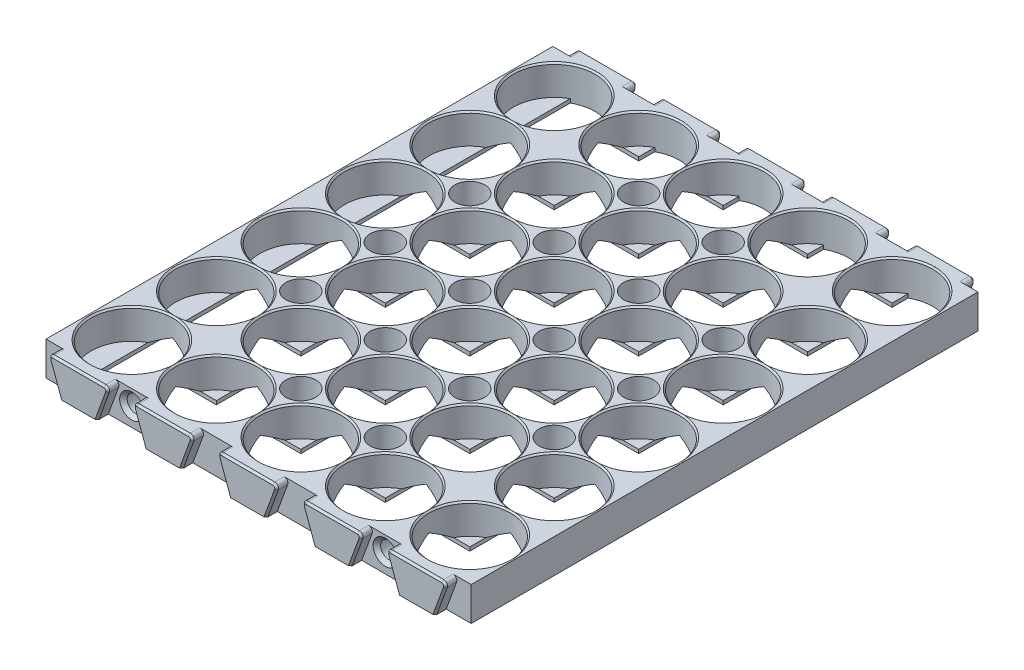
SolidWorks part; units mm, degrees
ref_plane "Front Plane" through (0, 0, 0) normal (0, 0, 1) x (1, 0, 0)
ref_plane "Top Plane" through (0, 0, 0) normal (0, 1, 0) x (1, 0, 0)
ref_plane "Right Plane" through (0, 0, 0) normal (1, 0, 0) x (0, 0, -1)
sketch "Sketch1" plane through (0, 0, 0) normal (0, 1, 0) x (1, 0, 0)
  line L0 (-11.25, 10.875) -> (11.25, 10.875) construction
  line L1 (-11.25, -11.25) -> (11.25, -11.25)
  line L2 (-11.25, -11.25) -> (-11.25, 11.25)
  line L3 (-11.25, 11.25) -> (11.25, 11.25)
  line L4 (11.25, -11.25) -> (11.25, 11.25)
  line L5 (-11.25, -11.25) -> (11.25, 11.25) construction
  line L6 (-11.25, 11.25) -> (11.25, -11.25) construction
  circle A0 centre (0, 0) radius 10.875
  point P0 (0, 0)
  dimension "D1" = 21.75
  dimension "D2" = 22.5
  dimension "D3" = 0.375
extrude "Boss-Extrude1" add sketch "Sketch1" along normal blind 8
sketch "Sketch2" plane through (0, 0, 0) normal (0, -1, 0) x (1, 0, 0)
  line L0 (5.25, 11.25) -> (-5.25, 11.25) construction
  line L1 (11.25, 11.25) -> (5.25, 11.25)
  line L2 (11.25, 11.25) -> (11.25, 5.25)
  line L3 (11.25, 5.25) -> (5.25, 5.25)
  line L4 (5.25, 11.25) -> (5.25, 5.25)
  line L5 (11.25, -11.25) -> (5.25, -11.25)
  line L6 (11.25, -11.25) -> (11.25, -5.25)
  line L7 (11.25, -5.25) -> (5.25, -5.25)
  line L8 (5.25, -11.25) -> (5.25, -5.25)
  line L9 (-11.25, -11.25) -> (-5.25, -11.25)
  line L10 (-11.25, -11.25) -> (-11.25, -5.25)
  line L11 (-11.25, -5.25) -> (-5.25, -5.25)
  line L12 (-5.25, -11.25) -> (-5.25, -5.25)
  line L13 (-11.25, 11.25) -> (-5.25, 11.25)
  line L14 (-11.25, 11.25) -> (-11.25, 5.25)
  line L15 (-11.25, 5.25) -> (-5.25, 5.25)
  line L16 (-5.25, 11.25) -> (-5.25, 5.25)
  line L17 (11.25, 5.25) -> (11.25, -5.25) construction
  line L18 (5.25, -11.25) -> (-5.25, -11.25) construction
  line L19 (-11.25, 5.25) -> (-11.25, -5.25) construction
  dimension "D1" = 10.5
extrude "Boss-Extrude2" add sketch "Sketch2" along normal blind 1
chamfer "Chamfer2" distance 0.4 angle 45 1 edges at (0, 8, 10.875)
pattern_linear "LPattern1" count 6 spacing 22.5 along (0, 0, 1) count 5 spacing 22.5 along (1, 0, 0) of "Boss-Extrude2", "Boss-Extrude1", "Chamfer2"
sketch "Sketch5" plane through (0, 0, -5.25) normal (0, 0, 1) x (1, 0, 0)
  line L25 (-5.25, -1) -> (-5.25, 0) construction
  line L26 (-5.25, -1) -> (-11.25, -1) construction
  line L27 (-11.25, -1) -> (-11.25, 0) construction
  line L29 (-5.25, 0) -> (-9.5238, 0) construction
  line L35 (-5.25, -1) -> (-5.25, 0)
  line L36 (-5.25, -1) -> (-11.25, -1)
  line L37 (-11.25, -1) -> (-11.25, 0)
  line L39 (-5.25, 0) -> (-11.25, 0)
  line L55 (101.25, -1) -> (95.25, -1)
  line L56 (101.25, -1) -> (101.25, 0)
  line L57 (101.25, 0) -> (95.25, 0)
  line L58 (95.25, -1) -> (95.25, 0)
  dimension "D1" = 6
extrude "Boss-Extrude3" add sketch "Sketch5" along normal up to surface (129 mm away)
sketch "Sketch6" plane through (0, 0, 0) normal (0, -1, 0) x (1, 0, 0)
  line L27 (39.75, -11.25) -> (50.25, -11.25) construction
  line L28 (50.25, -11.25) -> (50.25, -9.5238) construction
  line L29 (39.75, -9.5238) -> (39.75, -11.25) construction
  line L30 (17.25, -9.5238) -> (17.25, -11.25) construction
  line L31 (17.25, -11.25) -> (27.75, -11.25) construction
  line L32 (27.75, -11.25) -> (27.75, -9.5238) construction
  line L33 (-5.25, -9.5238) -> (-5.25, -11.25) construction
  line L34 (-5.25, -11.25) -> (5.25, -11.25) construction
  line L35 (5.25, -11.25) -> (5.25, -9.5238) construction
  line L51 (39.75, -11.25) -> (50.25, -11.25)
  line L52 (50.25, -11.25) -> (50.25, -9.5238)
  line L53 (39.75, -9.5238) -> (39.75, -11.25)
  line L54 (17.25, -9.5238) -> (17.25, -11.25)
  line L55 (17.25, -11.25) -> (27.75, -11.25)
  line L56 (27.75, -11.25) -> (27.75, -9.5238)
  line L57 (-5.25, -9.5238) -> (-5.25, -11.25)
  line L58 (-5.25, -11.25) -> (5.25, -11.25)
  line L59 (5.25, -11.25) -> (5.25, -9.5238)
  line L63 (50.25, 122.0238) -> (50.25, 123.75) construction
  line L64 (50.25, 123.75) -> (39.75, 123.75) construction
  line L65 (39.75, 123.75) -> (39.75, 122.0238) construction
  line L66 (27.75, 122.0238) -> (27.75, 123.75) construction
  line L67 (27.75, 123.75) -> (17.25, 123.75) construction
  line L68 (17.25, 123.75) -> (17.25, 122.0238) construction
  line L69 (5.25, 123.75) -> (-5.25, 123.75) construction
  line L70 (-5.25, 123.75) -> (-5.25, 122.0238) construction
  line L71 (5.25, 122.0238) -> (5.25, 123.75) construction
  line L75 (50.25, 122.0238) -> (50.25, 123.75)
  line L76 (50.25, 123.75) -> (39.75, 123.75)
  line L77 (39.75, 123.75) -> (39.75, 122.0238)
  line L78 (27.75, 122.0238) -> (27.75, 123.75)
  line L79 (27.75, 123.75) -> (17.25, 123.75)
  line L80 (17.25, 123.75) -> (17.25, 122.0238)
  line L81 (5.25, 123.75) -> (-5.25, 123.75)
  line L82 (-5.25, 123.75) -> (-5.25, 122.0238)
  line L83 (5.25, 122.0238) -> (5.25, 123.75)
  line L84 (84.75, -11.25) -> (95.25, -11.25) construction
  line L85 (95.25, -11.25) -> (95.25, -9.5238) construction
  line L86 (84.75, -9.5238) -> (84.75, -11.25) construction
  line L87 (95.25, 122.0238) -> (95.25, 123.75) construction
  line L88 (95.25, 123.75) -> (84.75, 123.75) construction
  line L89 (84.75, 123.75) -> (84.75, 122.0238) construction
  line L90 (72.75, 122.0238) -> (72.75, 123.75) construction
  line L91 (72.75, 123.75) -> (62.25, 123.75) construction
  line L92 (62.25, 123.75) -> (62.25, 122.0238) construction
  line L93 (84.75, -11.25) -> (95.25, -11.25)
  line L94 (95.25, -11.25) -> (95.25, -9.5238)
  line L95 (84.75, -9.5238) -> (84.75, -11.25)
  line L96 (95.25, 122.0238) -> (95.25, 123.75)
  line L97 (95.25, 123.75) -> (84.75, 123.75)
  line L98 (84.75, 123.75) -> (84.75, 122.0238)
  line L99 (72.75, 122.0238) -> (72.75, 123.75)
  line L100 (72.75, 123.75) -> (62.25, 123.75)
  line L101 (62.25, 123.75) -> (62.25, 122.0238)
  line L105 (62.25, -11.25) -> (72.75, -11.25)
  line L106 (72.75, -11.25) -> (72.75, -9.5238)
  line L107 (62.25, -9.5238) -> (62.25, -11.25)
  line L108 (62.25, -11.25) -> (72.75, -11.25)
  line L109 (72.75, -11.25) -> (72.75, -9.5238)
  line L110 (62.25, -9.5238) -> (62.25, -11.25)
  arc A9 (39.75, -9.5238) -> (50.25, -9.5238) centre (45, 0) ccw construction
  arc A10 (17.25, -9.5238) -> (27.75, -9.5238) centre (22.5, 0) ccw construction
  arc A11 (-5.25, -9.5238) -> (5.25, -9.5238) centre (0, 0) ccw construction
  arc A17 (39.75, -9.5238) -> (50.25, -9.5238) centre (45, 0) ccw
  arc A18 (17.25, -9.5238) -> (27.75, -9.5238) centre (22.5, 0) ccw
  arc A19 (-5.25, -9.5238) -> (5.25, -9.5238) centre (0, 0) ccw
  arc A21 (50.25, 122.0238) -> (39.75, 122.0238) centre (45, 112.5) ccw construction
  arc A22 (27.75, 122.0238) -> (17.25, 122.0238) centre (22.5, 112.5) ccw construction
  arc A23 (5.25, 122.0238) -> (-5.25, 122.0238) centre (0, 112.5) ccw construction
  arc A25 (50.25, 122.0238) -> (39.75, 122.0238) centre (45, 112.5) ccw
  arc A26 (27.75, 122.0238) -> (17.25, 122.0238) centre (22.5, 112.5) ccw
  arc A27 (5.25, 122.0238) -> (-5.25, 122.0238) centre (0, 112.5) ccw
  arc A28 (84.75, -9.5238) -> (95.25, -9.5238) centre (90, 0) ccw construction
  arc A29 (95.25, 122.0238) -> (84.75, 122.0238) centre (90, 112.5) ccw construction
  arc A30 (72.75, 122.0238) -> (62.25, 122.0238) centre (67.5, 112.5) ccw construction
  arc A31 (84.75, -9.5238) -> (95.25, -9.5238) centre (90, 0) ccw
  arc A32 (95.25, 122.0238) -> (84.75, 122.0238) centre (90, 112.5) ccw
  arc A33 (72.75, 122.0238) -> (62.25, 122.0238) centre (67.5, 112.5) ccw
  arc A35 (62.25, -9.5238) -> (72.75, -9.5238) centre (67.5, 0) ccw
  arc A36 (62.25, -9.5238) -> (72.75, -9.5238) centre (67.5, 0) ccw
  dimension "D1" = 0
extrude "Boss-Extrude4" add sketch "Sketch6" along normal up to surface (1 mm away) up to face at (-8.25, -1, 56.25)
sketch "Sketch7" plane through (0, 0, 0) normal (0, 0, 1) x (1, 0, 0)
  line L0 (84.75, 0) -> (90, 3.0311)
  line L1 (-5.25, 0) -> (5.25, 0)
  line L2 (-5.25, 0) -> (0, 5.25) construction
  line L3 (0, 5.25) -> (5.25, 0) construction
  line L4 (0, 0) -> (0, 7.975) construction
  line L5 (90, 3.0311) -> (95.25, 0)
  line L6 (-5.25, 0) -> (0, 3.0311)
  line L7 (0, 3.0311) -> (5.25, 0)
  line L8 (84.75, 0) -> (95.25, 0)
  line L9 (-5.25, -1) -> (-5.25, 0) construction
  line L10 (5.25, -1) -> (5.25, 0) construction
  line L11 (-5.25, -1) -> (-5.25, 0) construction
  line L12 (5.25, -1) -> (5.25, 0) construction
  line L13 (17.25, 0) -> (22.5, 3.0311)
  line L14 (22.5, 3.0311) -> (27.75, 0)
  line L15 (17.25, 0) -> (27.75, 0)
  line L16 (39.75, 0) -> (45, 3.0311)
  line L17 (45, 3.0311) -> (50.25, 0)
  line L18 (39.75, 0) -> (50.25, 0)
  line L19 (62.25, 0) -> (67.5, 3.0311)
  line L20 (67.5, 3.0311) -> (72.75, 0)
  line L21 (62.25, 0) -> (72.75, 0)
  line L22 (-5.25, 0) -> (17.25, 0) construction
  parabola Q0 (0.7504, 8) -> (-0.7504, 8) focus (0, 13.6125) apex (0, 7.975) construction
  dimension "D1" = 45
  dimension "D2" = 30
  dimension "D3" = 4.9439
  dimension "D5" = 22.5
  dimension "D4" = 5
extrude "Cut-Extrude1" cut sketch "Sketch7" along normal up to surface (117.75 mm away)
sketch "Sketch16" plane through (0, 0, 0) normal (1, 0, 0) x (0, 0, -1)
  line L2 (-5.25, -1) -> (-5.25, 0) construction
  line L3 (5.25, -1) -> (5.25, 0) construction
  line L4 (-5.25, 0) -> (0, 3.0311)
  line L5 (0, 3.0311) -> (5.25, 0)
  line L6 (-5.25, 0) -> (5.25, 0)
  line L7 (-5.25, -1) -> (-5.25, 0) construction
  line L8 (5.25, -1) -> (5.25, 0) construction
  line L9 (-22.5, 3.0311) -> (-17.25, 0)
  line L10 (-27.75, 0) -> (-17.25, 0)
  line L11 (-27.75, 0) -> (-22.5, 3.0311)
  line L12 (-45, 3.0311) -> (-39.75, 0)
  line L13 (-50.25, 0) -> (-39.75, 0)
  line L14 (-50.25, 0) -> (-45, 3.0311)
  line L15 (-67.5, 3.0311) -> (-62.25, 0)
  line L16 (-72.75, 0) -> (-62.25, 0)
  line L17 (-72.75, 0) -> (-67.5, 3.0311)
  line L18 (-90, 3.0311) -> (-84.75, 0)
  line L19 (-95.25, 0) -> (-84.75, 0)
  line L20 (-95.25, 0) -> (-90, 3.0311)
  line L21 (-112.5, 3.0311) -> (-107.25, 0)
  line L22 (-117.75, 0) -> (-107.25, 0)
  line L23 (-117.75, 0) -> (-112.5, 3.0311)
  line L24 (-135, 3.0311) -> (-129.75, 0)
  line L25 (-140.25, 0) -> (-129.75, 0)
  line L26 (-140.25, 0) -> (-135, 3.0311)
  line L27 (-157.5, 3.0311) -> (-152.25, 0)
  line L28 (-162.75, 0) -> (-152.25, 0)
  line L29 (-162.75, 0) -> (-157.5, 3.0311)
  line L30 (-180, 3.0311) -> (-174.75, 0)
  line L31 (-185.25, 0) -> (-174.75, 0)
  line L32 (-185.25, 0) -> (-180, 3.0311)
  line L33 (-202.5, 3.0311) -> (-197.25, 0)
  line L34 (-207.75, 0) -> (-197.25, 0)
  line L35 (-207.75, 0) -> (-202.5, 3.0311)
  line L36 (-225, 3.0311) -> (-219.75, 0)
  line L37 (-230.25, 0) -> (-219.75, 0)
  line L38 (-230.25, 0) -> (-225, 3.0311)
  line L39 (-247.5, 3.0311) -> (-242.25, 0)
  line L40 (-252.75, 0) -> (-242.25, 0)
  line L41 (-252.75, 0) -> (-247.5, 3.0311)
  line L42 (0, 3.0311) -> (-22.5, 3.0311) construction
  dimension "D1" = 30
  dimension "D3" = 22.5
  dimension "D2" = 12
extrude "Cut-Extrude7" cut sketch "Sketch16" along normal up to surface (84.75 mm away) up to face at (84.75, -0.3333, 11.25)
sketch "Sketch8" plane through (0, 0, -11.25) normal (0, 0, -1) x (-1, 0, 0)
  line L0 (0, -1) -> (0, 8) construction
  line L1 (-27.4743, -1) -> (-30.75, 8)
  line L2 (0.7504, 8) -> (11.25, 8) construction
  line L3 (4.9743, -1) -> (-4.9743, -1)
  line L4 (-4.9743, -1) -> (-8.25, 8)
  line L5 (-8.25, 8) -> (8.25, 8)
  line L6 (4.9743, -1) -> (8.25, 8)
  line L7 (11.25, 8) -> (11.25, -1) construction
  line L8 (11.25, -1) -> (-101.25, -1) construction
  line L9 (-30.75, 8) -> (-14.25, 8)
  line L10 (0.7504, 8) -> (11.25, 8) construction
  line L11 (-17.5257, -1) -> (-14.25, 8)
  line L12 (-17.5257, -1) -> (-27.4743, -1)
  line L13 (-49.9743, -1) -> (-53.25, 8)
  line L14 (-53.25, 8) -> (-36.75, 8)
  line L15 (-40.0257, -1) -> (-36.75, 8)
  line L16 (-40.0257, -1) -> (-49.9743, -1)
  line L17 (-72.4743, -1) -> (-75.75, 8)
  line L18 (-75.75, 8) -> (-59.25, 8)
  line L19 (-62.5257, -1) -> (-59.25, 8)
  line L20 (-62.5257, -1) -> (-72.4743, -1)
  line L21 (-4.9743, -1) -> (-27.4743, -1) construction
  line L22 (0.7504, 8) -> (11.25, 8) construction
  line L23 (-94.9743, -1) -> (-98.25, 8)
  line L24 (-98.25, 8) -> (-81.75, 8)
  line L25 (-85.0257, -1) -> (-81.75, 8)
  line L26 (-85.0257, -1) -> (-94.9743, -1)
  dimension "D1" = 70
  dimension "D2" = 3
  dimension "D4" = 22.5
  dimension "D5" = 9
sketch "Sketch9" plane through (0, 0, 123.75) normal (0, 0, 1) x (1, 0, 0)
  line L0 (94.9743, -1) -> (98.25, 8) construction
  line L3 (85.0257, -1) -> (81.75, 8) construction
  line L20 (85.0257, -1) -> (94.9743, -1) construction
  line L21 (98.25, 8) -> (81.75, 8) construction
  line L22 (94.9743, -1) -> (98.25, 8)
  line L23 (85.0257, -1) -> (81.75, 8)
  line L24 (-4.9743, -1) -> (4.9743, -1)
  line L25 (4.9743, -1) -> (8.25, 8)
  line L26 (8.25, 8) -> (-8.25, 8)
  line L27 (-8.25, 8) -> (-4.9743, -1)
  line L28 (-4.9743, -1) -> (4.9743, -1)
  line L29 (4.9743, -1) -> (8.25, 8)
  line L30 (8.25, 8) -> (-8.25, 8)
  line L31 (-8.25, 8) -> (-4.9743, -1)
  line L32 (72.4743, -1) -> (75.75, 8)
  line L33 (75.75, 8) -> (59.25, 8)
  line L34 (59.25, 8) -> (62.5257, -1)
  line L35 (62.5257, -1) -> (72.4743, -1)
  line L36 (72.4743, -1) -> (75.75, 8)
  line L37 (75.75, 8) -> (59.25, 8)
  line L38 (59.25, 8) -> (62.5257, -1)
  line L39 (62.5257, -1) -> (72.4743, -1)
  line L40 (49.9743, -1) -> (53.25, 8)
  line L41 (53.25, 8) -> (36.75, 8)
  line L42 (36.75, 8) -> (40.0257, -1)
  line L43 (40.0257, -1) -> (49.9743, -1)
  line L44 (49.9743, -1) -> (53.25, 8)
  line L45 (53.25, 8) -> (36.75, 8)
  line L46 (36.75, 8) -> (40.0257, -1)
  line L47 (40.0257, -1) -> (49.9743, -1)
  line L48 (14.25, 8) -> (17.5257, -1)
  line L49 (17.5257, -1) -> (27.4743, -1)
  line L50 (27.4743, -1) -> (30.75, 8)
  line L51 (30.75, 8) -> (14.25, 8)
  line L52 (14.25, 8) -> (17.5257, -1)
  line L53 (17.5257, -1) -> (27.4743, -1)
  line L54 (27.4743, -1) -> (30.75, 8)
  line L55 (30.75, 8) -> (14.25, 8)
  line L56 (85.0257, -1) -> (94.9743, -1)
  line L57 (98.25, 8) -> (81.75, 8)
  dimension "D1" = 0
  dimension "D2" = 0
  dimension "D3" = 0
  dimension "D4" = 0
extrude "Boss-Extrude5" add sketch "Sketch8" along normal blind 3
extrude "Boss-Extrude6" add sketch "Sketch9" along normal blind 3
fillet "Fillet1" radius 1 20 edges at (-8.25, 8, 125.25) (8.25, 8, 125.25) (14.25, 8, 125.25) (30.75, 8, 125.25) (36.75, 8, 125.25) (53.25, 8, 125.25) (59.25, 8, 125.25) (75.75, 8, 125.25) (81.75, 8, 125.25) (98.25, 8, 125.25) (98.25, 8, -12.75) (81.75, 8, -12.75) (75.75, 8, -12.75) (59.25, 8, -12.75) (53.25, 8, -12.75) (36.75, 8, -12.75) (30.75, 8, -12.75) (14.25, 8, -12.75) (8.25, 8, -12.75) (-8.25, 8, -12.75)
chamfer "Chamfer3" distance 0.5 angle 45 50 edges at (6.3679, 2.829, -14.25) (0, 8, -14.25) (-6.3679, 2.829, -14.25) (73.8679, 2.829, -14.25) (67.5, 8, -14.25) (61.1321, 2.829, -14.25) (51.3679, 2.829, -14.25) (45, 8, -14.25) (38.6321, 2.829, -14.25) (28.8679, 2.829, -14.25) (22.5, 8, -14.25) (16.1321, 2.829, -14.25) (73.8679, 2.829, 126.75) (61.1321, 2.829, 126.75) (67.5, 8, 126.75) (51.3679, 2.829, 126.75) (38.6321, 2.829, 126.75) (45, 8, 126.75) (28.8679, 2.829, 126.75) (16.1321, 2.829, 126.75) (22.5, 8, 126.75) (6.3679, 2.829, 126.75) (-6.3679, 2.829, 126.75) (0, 8, 126.75) (96.3679, 2.829, -14.25) (90, 8, -14.25) (83.6321, 2.829, -14.25) (83.6321, 2.829, 126.75) (96.3679, 2.829, 126.75) (90, 8, 126.75) (97.641, 7.5736, -14.25) (82.359, 7.5736, -14.25) (97.641, 7.5736, 126.75) (82.359, 7.5736, 126.75) (75.141, 7.5736, 126.75) (59.859, 7.5736, 126.75) (52.641, 7.5736, 126.75) (37.359, 7.5736, 126.75) (30.141, 7.5736, 126.75) (14.859, 7.5736, 126.75) (7.641, 7.5736, 126.75) (-7.641, 7.5736, 126.75) (75.141, 7.5736, -14.25) (59.859, 7.5736, -14.25) (52.641, 7.5736, -14.25) (37.359, 7.5736, -14.25) (30.141, 7.5736, -14.25) (14.859, 7.5736, -14.25) (7.641, 7.5736, -14.25) (-7.641, 7.5736, -14.25)
sketch "Sketch10" plane through (0, 0, -11.25) normal (0, 0, -1) x (-1, 0, 0)
  line L0 (-11.25, -1) -> (-11.25, 8) construction
  line L1 (-49.4422, -1) -> (-40.5578, -1) construction
  line L2 (-4.9743, -1) -> (-17.5257, -1) construction
  line L3 (-51.8219, 8) -> (-38.1781, 8) construction
  line L4 (-14.25, 8) -> (-8.25, 8) construction
  line L5 (-45, 8) -> (-45, -1) construction
  circle A0 centre (-11.25, 4) radius 2.25
  circle A1 centre (-78.75, 4) radius 2.25
  dimension "D2" = 4.5
  dimension "D1" = 4
sketch "Sketch11" plane through (0, 0, 123.75) normal (0, 0, 1) x (1, 0, 0)
  circle A0 centre (11.25, 4) radius 2.25 construction
  circle A1 centre (11.25, 4) radius 2.25
  circle A2 centre (78.75, 4) radius 2.25 construction
  circle A3 centre (78.75, 4) radius 2.25
extrude "Cut-Extrude2" cut sketch "Sketch10" against normal blind 5
extrude "Cut-Extrude3" cut sketch "Sketch11" against normal blind 5
chamfer "Chamfer5" distance 1 angle 45 4 edges at (81, 4, -11.25) (9, 4, -11.25) (81, 4, 123.75) (13.5, 4, 123.75)
sketch "Sketch17" plane through (0, -1, 0) normal (0, -1, 0) x (1, 0, 0)
  line L0 (5.25, 5.25) -> (17.25, 17.25) construction
  line L1 (11.25, 11.25) -> (33.75, 11.25) construction
  line L2 (11.25, 11.25) -> (11.25, 33.75) construction
  circle A0 centre (11.25, 11.25) radius 4 construction
  circle A1 centre (33.75, 11.25) radius 4
  circle A2 centre (56.25, 11.25) radius 4
  circle A3 centre (33.75, 33.75) radius 4
  circle A4 centre (56.25, 33.75) radius 4
  circle A5 centre (33.75, 56.25) radius 4
  circle A6 centre (56.25, 56.25) radius 4
  circle A7 centre (33.75, 78.75) radius 4
  circle A8 centre (56.25, 78.75) radius 4
  circle A9 centre (33.75, 101.25) radius 4
  circle A10 centre (56.25, 101.25) radius 4
  circle A23 centre (11.25, 33.75) radius 4
  circle A24 centre (11.25, 56.25) radius 4
  circle A25 centre (11.25, 78.75) radius 4
  circle A26 centre (11.25, 101.25) radius 4 construction
  circle A51 centre (78.75, 11.25) radius 4 construction
  circle A52 centre (78.75, 33.75) radius 4
  circle A53 centre (78.75, 56.25) radius 4
  circle A54 centre (78.75, 78.75) radius 4
  circle A55 centre (78.75, 101.25) radius 4 construction
  dimension "D5" = 22.5
  dimension "D4" = 22.5
  dimension "D1" = 8
  dimension "D2" = 4
extrude "Cut-Extrude8" cut sketch "Sketch17" against normal through all
sketch "Sketch18" plane through (0, -1, 0) normal (0, -1, 0) x (1, 0, 0)
  line L0 (72.75, 17.25) -> (72.75, 5.25) construction
  line L1 (84.75, 17.25) -> (72.75, 17.25) construction
  line L2 (101.25, -11.25) -> (101.25, 123.75) construction
  line L34 (72.75, 17.25) -> (84.75, 5.25) construction
  line L35 (5.25, 17.25) -> (17.25, 5.25) construction
  line L36 (17.25, 5.25) -> (17.25, 17.25) construction
  line L37 (5.25, 5.25) -> (17.25, 5.25) construction
  line L38 (101.25, 56.25) -> (-11.25, 56.25) construction
  line L40 (-11.25, 123.75) -> (-11.25, -11.25) construction
  line L41 (5.25, 95.25) -> (17.25, 107.25) construction
  line L42 (72.75, 95.25) -> (84.75, 107.25) construction
  circle A0 centre (11.25, 11.25) radius 2.1
  circle A1 centre (78.75, 11.25) radius 2.1
  circle A5 centre (78.75, 101.25) radius 2.1
  circle A6 centre (11.25, 101.25) radius 2.1
  dimension "D3" = 45
  dimension "D1" = 4.2
  dimension "D2" = 67.5
extrude "Cut-Extrude9" cut sketch "Sketch18" against normal blind 4
sketch "Sketch19" plane through (0, -1, 0) normal (0, -1, 0) x (1, 0, 0)
  line L0 (101.25, 56.25) -> (-11.25, 56.25) construction
  line L2 (-11.25, 123.75) -> (-11.25, -11.25) construction
  line L3 (101.25, -11.25) -> (101.25, 123.75) construction
  circle A2 centre (78.75, 11.25) radius 1.7
  circle A3 centre (11.25, 11.25) radius 1.7
  circle A4 centre (11.25, 101.25) radius 1.7
  circle A5 centre (78.75, 101.25) radius 1.7
  dimension "D1" = 3.4
extrude "Cut-Extrude10" cut sketch "Sketch19" against normal offset from surface (7 mm away) 2 up to face at (78.75, 8, 74.75)
chamfer "Chamfer6" distance 1 angle 45 4 edges at (11.25, -1, 103.35) (11.25, -1, 9.15) (78.75, -1, 9.15) (78.75, -1, 103.35)
sketch "Sketch22" plane through (0, 8, 0) normal (0, 1, 0) x (1, 0, 0)
  line L0 (38.1781, 14.25) -> (51.8219, 14.25) construction
  line L1 (-11.25, 11.25) -> (-11.625, 11.25)
  line L2 (-11.25, 11.25) -> (-11.25, -123.75)
  line L3 (-11.25, -123.75) -> (-11.625, -123.75)
  line L4 (-11.625, 11.25) -> (-11.625, -123.75)
  line L5 (45, 14.25) -> (45, -126.75) construction
  line L7 (51.8219, -126.75) -> (38.1781, -126.75) construction
  line L13 (-4.9743, -123.75) -> (-11.25, -123.75) construction
  line L14 (101.625, 11.25) -> (101.625, -123.75)
  line L15 (101.25, -123.75) -> (101.625, -123.75)
  line L16 (101.25, 11.25) -> (101.25, -123.75)
  line L17 (101.25, 11.25) -> (101.625, 11.25)
  arc A1 (-5.25, 9.5238) -> (-5.25, -9.5238) centre (0, 0) ccw construction
  point P10 (-10.875, 0)
  dimension "D1" = 0.75
  dimension "D2" = 0.375
extrude "Boss-Extrude7" add sketch "Sketch22" against normal up to surface (9 mm away) up to face at (45, -1, 56.25)
sketch "Sketch14" plane through (0, -1, 0) normal (0, -1, 0) x (1, 0, 0)
  line L0 (45, -14.25) -> (45, 126.75) construction
  line L2 (-5.25, 101.25) -> (-6.25, 101.25) construction
  line L3 (49.4422, -14.25) -> (40.5578, -14.25) construction
  line L4 (40.5578, 126.75) -> (49.4422, 126.75) construction
  line L19 (-10.25, 53.7941) -> (-10.25, 58.7059)
  line L30 (-6.25, 101.25) -> (-10.25, 101.25) construction
  line L39 (-6.25, 55.25) -> (-6.25, 57.25)
  line L40 (-6.25, 10.25) -> (-6.25, 12.25)
  line L51 (-10.25, 8.7941) -> (-10.25, 13.7059)
  line L52 (-10.25, 101.25) -> (-11.625, 101.25) construction
  line L53 (-10.25, 58.7059) -> (-6.25, 57.25)
  line L54 (-10.25, 103.7059) -> (-6.25, 102.25)
  line L57 (-10.25, 13.7059) -> (-6.25, 12.25)
  line L58 (-5.25, -9.5238) -> (-5.25, 122.0238) construction
  line L59 (-10.25, 98.7941) -> (-6.25, 100.25)
  line L60 (-10.25, 103.7059) -> (-10.25, 98.7941)
  line L61 (-6.25, 102.25) -> (-6.25, 100.25)
  line L62 (95.25, 56.25) -> (96.25, 56.25) construction
  line L64 (96.25, 56.25) -> (100.25, 56.25) construction
  line L65 (100.25, 56.25) -> (101.625, 56.25) construction
  line L66 (95.25, 11.25) -> (96.25, 11.25) construction
  line L67 (96.25, 11.25) -> (100.25, 11.25) construction
  line L68 (-5.25, 9.5238) -> (-5.25, 12.9762) construction
  line L69 (-10.25, 11.25) -> (-11.625, 11.25) construction
  line L70 (-6.25, 11.25) -> (-10.25, 11.25) construction
  line L71 (-5.25, 11.25) -> (-6.25, 11.25) construction
  line L75 (-10.25, 8.7941) -> (-6.25, 10.25)
  line L76 (100.25, 11.25) -> (101.625, 11.25) construction
  line L77 (100.25, 101.25) -> (101.625, 101.25) construction
  line L78 (96.25, 101.25) -> (100.25, 101.25) construction
  line L79 (95.25, 101.25) -> (96.25, 101.25) construction
  line L84 (100.25, 53.7941) -> (96.25, 55.25)
  line L85 (100.25, 8.7941) -> (96.25, 10.25)
  line L86 (96.25, 102.25) -> (96.25, 100.25)
  line L87 (100.25, 103.7059) -> (100.25, 98.7941)
  line L93 (-10.25, 56.25) -> (-11.625, 56.25) construction
  line L94 (-6.25, 56.25) -> (-10.25, 56.25) construction
  line L95 (-5.25, 56.25) -> (-6.25, 56.25) construction
  line L98 (-10.25, 53.7941) -> (-6.25, 55.25)
  line L99 (100.25, 98.7941) -> (96.25, 100.25)
  line L100 (100.25, 13.7059) -> (96.25, 12.25)
  line L101 (100.25, 103.7059) -> (96.25, 102.25)
  line L102 (100.25, 58.7059) -> (96.25, 57.25)
  line L103 (100.25, 8.7941) -> (100.25, 13.7059)
  line L104 (96.25, 10.25) -> (96.25, 12.25)
  line L105 (96.25, 55.25) -> (96.25, 57.25)
  line L106 (100.25, 53.7941) -> (100.25, 58.7059)
  line L111 (-11.625, -11.25) -> (-11.625, 123.75) construction
  dimension "D1" = 70
  dimension "D2" = 1.375
  dimension "D3" = 1
  dimension "D5" = 4
  dimension "D6" = 56.625
  dimension "D7" = 70
  dimension "D8" = 2.4559
  dimension "D9" = 1
extrude "Cut-Extrude11" cut sketch "Sketch14" against normal blind 2
chamfer "Chamfer7" distance 0.5 angle 45 24 edges at (-6.25, -1, 101.25) (-8.25, -1, 99.5221) (-10.25, -1, 101.25) (-8.25, -1, 102.9779) (98.25, -1, 99.5221) (100.25, -1, 101.25) (96.25, -1, 101.25) (98.25, -1, 102.9779) (100.25, -1, 56.25) (98.25, -1, 54.5221) (96.25, -1, 56.25) (98.25, -1, 57.9779) (98.25, -1, 9.5221) (100.25, -1, 11.25) (96.25, -1, 11.25) (98.25, -1, 12.9779) (-10.25, -1, 56.25) (-8.25, -1, 54.5221) (-6.25, -1, 56.25) (-8.25, -1, 57.9779) (-10.25, -1, 11.25) (-8.25, -1, 12.9779) (-6.25, -1, 11.25) (-8.25, -1, 9.5221)
equation "\"cell_side\"= 22.50"
equation "\"D2@Sketch1\"=\"cell_side\""
equation "\"D5@Sketch7\"=\"cell_side\""
equation "\"D3@Sketch16\"=\"cell_side\""
equation "\"D4@Sketch8\"=\"cell_side\""
equation "\"D5@Sketch17\"=\"cell_side\""
equation "\"D3@LPattern1\"=\"cell_side\""
equation "\"D4@LPattern1\"=\"cell_side\""
equation "\"D4@Sketch17\"=\"cell_side\""
